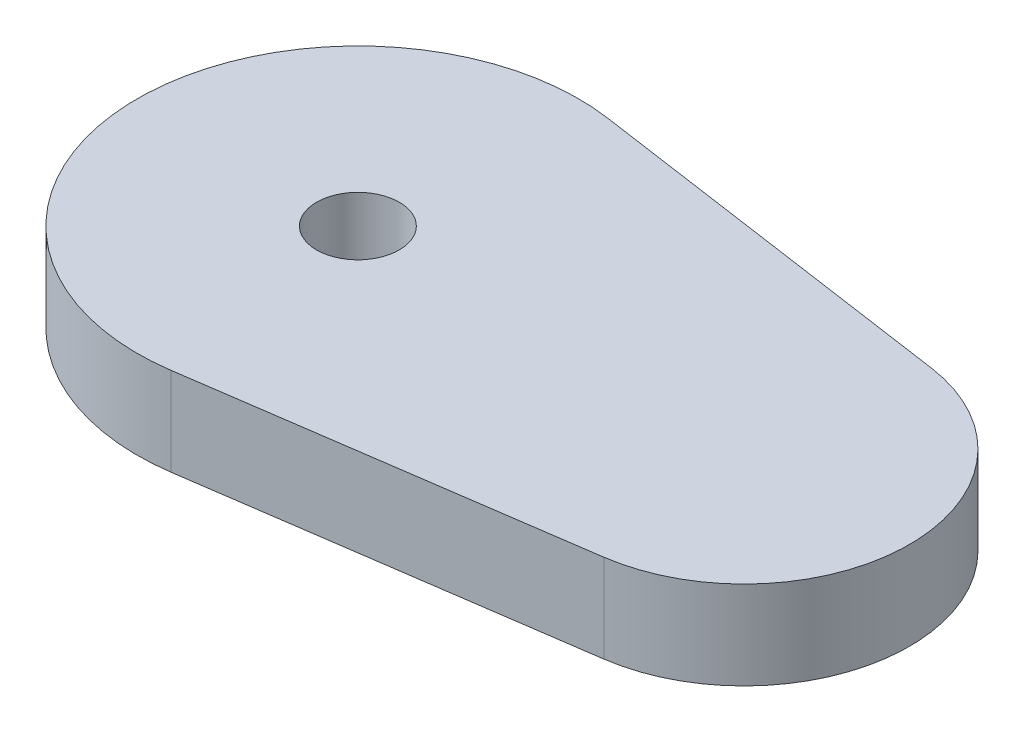
SolidWorks part; units mm, degrees
ref_plane "Front Plane" through (0, 0, 0) normal (0, 0, 1) x (1, 0, 0)
ref_plane "Top Plane" through (0, 0, 0) normal (0, 1, 0) x (1, 0, 0)
ref_plane "Right Plane" through (0, 0, 0) normal (1, 0, 0) x (0, 0, -1)
sketch "Sketch1" plane through (0, 0, 0) normal (0, 1, 0) x (1, 0, 0)
  line L0 (0, 0) -> (14, 0) construction
  line L6 (1.1429, -7.9179) -> (14.8571, -5.9385)
  line L8 (1.1429, 7.9179) -> (14.8571, 5.9385)
  line L11 (14, 0) -> (20, 0) construction
  circle A0 centre (0, 0) radius 1.5
  arc A1 (1.1429, 7.9179) -> (1.1429, -7.9179) centre (0, 0) ccw
  arc A2 (14.8571, 5.9385) -> (14.8571, -5.9385) centre (14, 0) cw
  dimension "D1" = 3
  dimension "D2" = 20
  dimension "D5" = 8
  dimension "D6" = 6
  dimension "D3" = 8
sketch "Sketch2" plane through (0, 0, 0) normal (0, 0, 1) x (1, 0, 0)
  line L0 (0, 0) -> (0, 3.2) construction
  dimension "D1" = 3.2
extrude "Boss-Extrude1" add sketch "Sketch1" along normal up to vertex (3.2 mm away) up to point (0, 3.2, 0)
equation "\"glass_width\" = 150"
equation "\"glass_height\"= 100"
equation "\"glass_thickness\"= 4"
equation "\"brood_space\"= 42"
equation "\"t1\"= 6"
equation "\"t2\"= 3.2"
equation "\"box_depth\"= \"brood_space\" + \"glass_thickness\" + \"glass_thickness\" + \"t2\" + \"t2\""
equation "\"box_width\"= \"glass_width\" + \"t1\" + \"t1\""
equation "\"food_height\"= 70"
equation "\"box_height\" = \"glass_height\" + ( \"t1\" * 3 ) + \"food_height\""
equation "\"D1@Sketch2\"=\"t2\""
